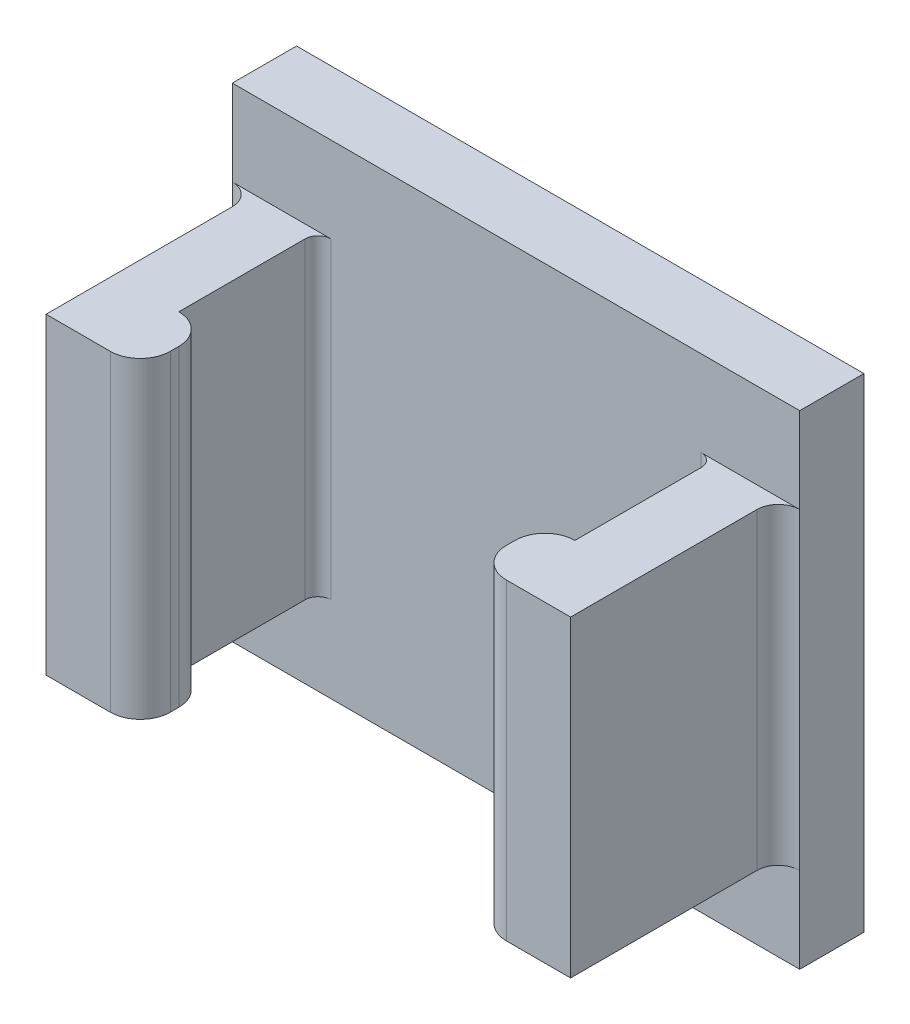
SolidWorks part; units mm, degrees
ref_plane "정면" through (0, 0, 0) normal (0, 0, 1) x (1, 0, 0)
ref_plane "윗면" through (0, 0, 0) normal (0, 1, 0) x (1, 0, 0)
ref_plane "우측면" through (0, 0, 0) normal (1, 0, 0) x (0, 0, -1)
sketch "스케치1" plane through (0, 0, 0) normal (0, 0, 1) x (1, 0, 0)
  line L1 (-6.125, -5.65) -> (6.125, -5.65)
  line L2 (-6.125, -5.65) -> (-6.125, 5.65)
  line L3 (-6.125, 5.65) -> (6.125, 5.65)
  line L4 (6.125, -5.65) -> (6.125, 5.65)
  line L5 (-6.125, -5.65) -> (6.125, 5.65) construction
  line L6 (-6.125, 5.65) -> (6.125, -5.65) construction
  point P0 (0, 0)
  dimension "D1" = 12.25
  dimension "D2" = 11.3
extrude "보스-돌출1" add sketch "스케치1" along normal blind 2.5
sketch "스케치2" plane through (0, 0, 2.5) normal (0, 0, 1) x (1, 0, 0)
  line L0 (-6.125, -5.65) -> (6.125, -5.65) construction
  line L1 (-6.125, 5.65) -> (-4.625, 5.65)
  line L2 (-6.125, 5.65) -> (-6.125, -5.65)
  line L3 (-6.125, -5.65) -> (-4.625, -5.65)
  line L4 (-4.625, 5.65) -> (-4.625, -5.65)
  line L6 (6.125, 5.65) -> (4.625, 5.65)
  line L7 (6.125, 5.65) -> (6.125, -5.65)
  line L8 (6.125, -5.65) -> (4.625, -5.65)
  line L9 (4.625, 5.65) -> (4.625, -5.65)
  dimension "D1" = 1.5
  dimension "D2" = 1.5
extrude "보스-돌출2" add sketch "스케치2" along normal blind 3.85
sketch "스케치5" plane through (0, 0, 2.5) normal (0, 0, 1) x (1, 0, 0)
  line L0 (4.625, 5.65) -> (4.625, -5.65) construction
  line L1 (-4.625, -5.75) -> (4.625, -5.75)
  line L2 (-4.625, -5.75) -> (-4.625, 5.75)
  line L3 (-4.625, 5.75) -> (4.625, 5.75)
  line L4 (4.625, -5.75) -> (4.625, 5.75)
  line L5 (-4.625, -5.75) -> (4.625, 5.75) construction
  line L6 (-4.625, 5.75) -> (4.625, -5.75) construction
  point P0 (0, 0)
  dimension "D1" = 11.5
extrude "컷-돌출1" cut sketch "스케치5" against normal blind 1
sketch "스케치8" plane through (-4.625, 0, 0) normal (1, 0, 0) x (0, 0, -1)
  line L0 (-6.35, -5.65) -> (-1.5, -5.65) construction
  line L1 (-6.35, 5.65) -> (-4.75, 5.65)
  line L2 (-6.35, 5.65) -> (-6.35, -5.65)
  line L3 (-6.35, -5.65) -> (-4.75, -5.65)
  line L4 (-4.75, 5.65) -> (-4.75, -5.65)
  dimension "D1" = 1.6
extrude "보스-돌출5" add sketch "스케치8" along normal blind 0.7
sketch "스케치9" plane through (4.625, 0, 0) normal (-1, 0, 0) x (0, 0, 1)
  line L0 (6.35, 5.65) -> (1.5, 5.65) construction
  line L1 (6.35, -5.65) -> (4.75, -5.65)
  line L2 (6.35, -5.65) -> (6.35, 5.65)
  line L3 (6.35, 5.65) -> (4.75, 5.65)
  line L4 (4.75, -5.65) -> (4.75, 5.65)
  dimension "D1" = 1.6
extrude "보스-돌출6" add sketch "스케치9" along normal blind 0.7
fillet "필렛8" radius 0.3 2 edges at (4.625, 0, 1.5) (-4.625, 0, 1.5)
sketch "스케치11" plane through (0, 5.65, 0) normal (0, 1, 0) x (1, 0, 0)
  line L0 (6.125, -6.35) -> (6.125, 0) construction
  line L1 (-6.125, -6.35) -> (6.125, -6.35)
  line L2 (-6.125, -6.35) -> (-6.125, -1.5)
  line L3 (-6.125, -1.5) -> (6.125, -1.5)
  line L4 (6.125, -6.35) -> (6.125, -1.5)
  line L5 (-4.325, -1.5) -> (4.325, -1.5) construction
  dimension "D1" = 0
extrude "컷-돌출2" cut sketch "스케치11" against normal blind 2
sketch "스케치12" plane through (0, -5.65, 0) normal (0, -1, 0) x (1, 0, 0)
  line L0 (6.125, 6.35) -> (6.125, 0) construction
  line L1 (-6.125, 6.35) -> (6.125, 6.35)
  line L2 (-6.125, 6.35) -> (-6.125, 1.5)
  line L3 (-6.125, 1.5) -> (6.125, 1.5)
  line L4 (6.125, 6.35) -> (6.125, 1.5)
  line L5 (4.325, 1.5) -> (-4.325, 1.5) construction
  dimension "D1" = 0
extrude "컷-돌출3" cut sketch "스케치12" against normal blind 2
sketch "스케치13" plane through (6.125, 0, 0) normal (1, 0, 0) x (0, 0, -1)
  line L1 (-1.5, 5.65) -> (0, 5.65)
  line L2 (-1.5, 5.65) -> (-1.5, -5.65)
  line L3 (-1.5, -5.65) -> (0, -5.65)
  line L4 (0, 5.65) -> (0, -5.65)
extrude "보스-돌출7" add sketch "스케치13" along normal blind 0.5
sketch "스케치14" plane through (-6.125, 0, 0) normal (-1, 0, 0) x (0, 0, 1)
  line L1 (1.5, 5.65) -> (0, 5.65)
  line L2 (1.5, 5.65) -> (1.5, -5.65)
  line L3 (1.5, -5.65) -> (0, -5.65)
  line L4 (0, 5.65) -> (0, -5.65)
extrude "보스-돌출8" add sketch "스케치14" along normal blind 0.5
fillet "필렛9" radius 0.5 2 edges at (6.125, 0, 1.5) (-6.125, 0, 1.5)
fillet "필렛10" radius 0.7 4 edges at (-3.925, 0, 6.35) (-3.925, 0, 4.75) (3.925, 0, 4.75) (3.925, 0, 6.35)
